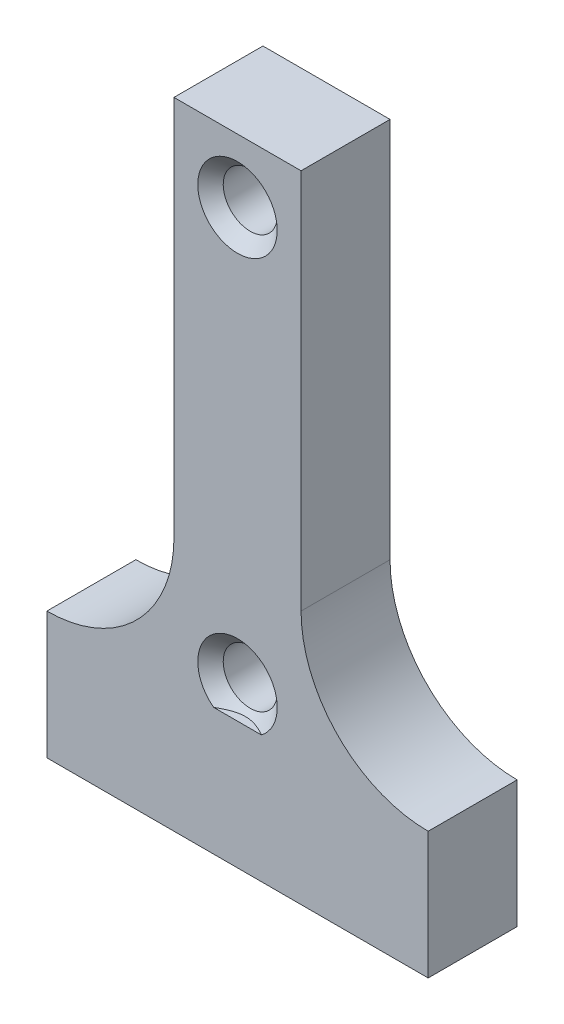
SolidWorks part; units mm, degrees
ref_plane "Front Plane" through (0, 0, 0) normal (0, 0, 1) x (1, 0, 0)
ref_plane "Top Plane" through (0, 0, 0) normal (0, 1, 0) x (1, 0, 0)
ref_plane "Right Plane" through (0, 0, 0) normal (1, 0, 0) x (0, 0, -1)
sketch "Sketch1" plane through (0, 0, 0) normal (0, 0, 1) x (1, 0, 0)
  line L1 (0, 0) -> (10, 0)
  line L2 (0, 0) -> (0, 40)
  line L3 (0, 40) -> (10, 40)
  line L4 (10, 0) -> (10, 40)
  dimension "D1" = 40
  dimension "D2" = 10
extrude "Boss-Extrude1" add sketch "Sketch1" along normal blind 7
sketch "Sketch2" plane through (0, 0, 7) normal (0, 0, 1) x (1, 0, 0)
  line L0 (10, 40) -> (0, 40) construction
  line L2 (10, 0) -> (10, 40) construction
  line L4 (0, 0) -> (10, 0) construction
  circle A2 centre (5, 35) radius 2.125
  circle A3 centre (5, 2.5) radius 2.125
  dimension "D1" = 5
  dimension "D4" = 5
  dimension "D5" = 2.5
extrude "Cut-Extrude1" cut sketch "Sketch2" against normal blind 7
chamfer "Chamfer1" distance 1 angle 45 2 edges at (7.125, 2.5, 7) (7.125, 35, 7)
sketch "Sketch3" plane through (0, 0, 0) normal (0, -1, 0) x (1, 0, 0)
  line L1 (-10, 7) -> (20, 7)
  line L2 (-10, 7) -> (-10, 0)
  line L3 (-10, 0) -> (20, 0)
  line L4 (20, 7) -> (20, 0)
  line L5 (0, 0) -> (10, 0) construction
  point P10 (5, 0)
  point P11 (5, 0)
  dimension "D1" = 30
extrude "Boss-Extrude2" add sketch "Sketch3" along normal blind 10
ref_axis "Axis1" through (5, 35, 0) along (0, 0, 1)
ref_axis "Axis2" through (5, 2.5, 0) along (0, 0, 1)
ref_plane "Plane1" through (0, 20, 0) normal (0, 1, 0) x (1, 0, 0)
ref_plane "Plane2" through (5, 0, 0) normal (-1, 0, 0) x (0, 0, 1)
ref_axis "Axis3" through (5, 20, 54.8218) along (0, 0, -1)
fillet "Fillet1" radius 10 2 edges at (0, 0, 3.5) (10, 0, 3.5)
